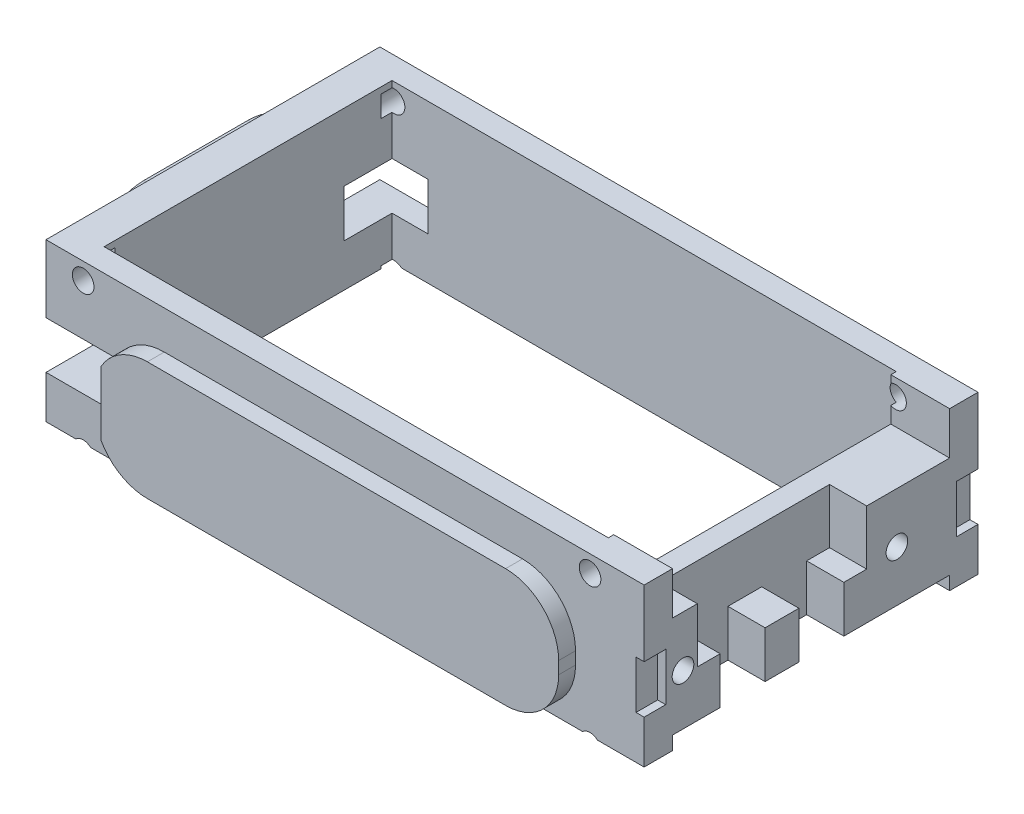
SolidWorks part; units mm, degrees
material "尼龙 101"
ref_plane "前视基准面" through (0, 0, 0) normal (0, 0, 1) x (1, 0, 0)
ref_plane "上视基准面" through (0, 0, 0) normal (0, 1, 0) x (1, 0, 0)
ref_plane "右视基准面" through (0, 0, 0) normal (1, 0, 0) x (0, 0, -1)
other "Configuration Table"
sketch "草图2" plane through (0, 0, 0) normal (0, 0, 1) x (1, 0, 0)
  line L1 (0, 0) -> (69, 0)
  line L2 (0, 0) -> (0, -17.83)
  line L3 (0, -17.83) -> (69, -17.83)
  line L4 (69, 0) -> (69, -17.83)
  dimension "D1" = 69
  dimension "D2" = 17.83
extrude "凸台-拉伸1" add sketch "草图2" along normal blind 2.5
fillet "圆角1" radius 8 4 edges at (69, 0, 1.25) (69, -17.83, 1.25) (0, -17.83, 1.25) (0, 0, 1.25)
sketch "草图3" plane through (0, 0, 0) normal (0, 0, -1) x (-1, 0, 0)
  line L0 (-61, 0) -> (-8, 0) construction
  line L1 (-79, 5.5) -> (9.5, 5.5)
  line L2 (-79, 5.5) -> (-79, -17.83)
  line L3 (-79, -17.83) -> (9.5, -17.83)
  line L4 (9.5, 5.5) -> (9.5, -17.83)
  line L5 (-8, -17.83) -> (-61, -17.83) construction
  line L6 (-69, -9.83) -> (-69, -8) construction
  line L7 (0, -8) -> (0, -9.83) construction
  dimension "D1" = 5.5
  dimension "D2" = 9.5
  dimension "D3" = 10
extrude "凸台-拉伸2" add sketch "草图3" along normal blind 4.2
sketch "草图4" plane through (-9.5, 0, 0) normal (-1, 0, 0) x (0, 0, 1)
  line L5 (-4.2, 5.5) -> (0, 5.5) construction
  line L6 (-4.2, -17.83) -> (-45.2, -17.83)
  line L7 (-4.2, -17.83) -> (-4.2, 5.5)
  line L8 (-4.2, 5.5) -> (-45.2, 5.5)
  line L9 (-45.2, -17.83) -> (-45.2, 5.5)
  dimension "D1" = 41
extrude "凸台-拉伸3" add sketch "草图4" against normal blind 6
sketch "草图5" plane through (0, 0, -45.2) normal (0, 0, -1) x (-1, 0, 0)
  line L1 (-79, 5.5) -> (9.5, 5.5)
  line L2 (-79, 5.5) -> (-79, -17.83)
  line L3 (-79, -17.83) -> (9.5, -17.83)
  line L4 (9.5, 5.5) -> (9.5, -17.83)
extrude "凸台-拉伸4" add sketch "草图5" along normal blind 4.2
sketch "草图6" plane through (0, 0, -49.4) normal (0, 0, -1) x (-1, 0, 0)
  line L4 (-69, -8) -> (-69, -9.83)
  line L5 (-8, 0) -> (-61, 0)
  line L6 (0, -9.83) -> (0, -8)
  line L7 (-61, -17.83) -> (-8, -17.83)
  line L8 (-69, -8) -> (-69, -9.83)
  line L9 (-8, 0) -> (-61, 0)
  line L10 (0, -9.83) -> (0, -8)
  line L11 (-61, -17.83) -> (-8, -17.83)
  arc A4 (-61, 0) -> (-69, -8) centre (-61, -8) ccw
  arc A5 (0, -8) -> (-8, 0) centre (-8, -8) ccw
  arc A6 (-8, -17.83) -> (0, -9.83) centre (-8, -9.83) ccw
  arc A7 (-69, -9.83) -> (-61, -17.83) centre (-61, -9.83) ccw
  arc A8 (-61, 0) -> (-69, -8) centre (-61, -8) ccw
  arc A9 (0, -8) -> (-8, 0) centre (-8, -8) ccw
  arc A10 (-8, -17.83) -> (0, -9.83) centre (-8, -9.83) ccw
  arc A11 (-69, -9.83) -> (-61, -17.83) centre (-61, -9.83) ccw
  dimension "D1" = 0
extrude "凸台-拉伸5" add sketch "草图6" along normal blind 2.5
sketch "草图7" plane through (-9.5, 0, 0) normal (-1, 0, 0) x (0, 0, 1)
  line L0 (-49.4, 0) -> (-49.4, -8) construction
  line L1 (-49.4, -4.5) -> (-38.9, -4.5)
  line L2 (-49.4, -4.5) -> (-49.4, -11.5)
  line L3 (-49.4, -11.5) -> (-38.9, -11.5)
  line L4 (-38.9, -4.5) -> (-38.9, -11.5)
  line L5 (-49.4, 5.5) -> (0, 5.5) construction
  line L6 (-24.7, 5.5) -> (-24.7, -17.83) construction
  line L7 (-49.4, -17.83) -> (0, -17.83) construction
  line L8 (0, -11.5) -> (-10.5, -11.5)
  line L9 (-10.5, -4.5) -> (-10.5, -11.5)
  line L10 (0, -4.5) -> (-10.5, -4.5)
  line L11 (0, -4.5) -> (0, -11.5)
  dimension "D1" = 10
  dimension "D2" = 10.5
  dimension "D3" = 7
extrude "切除-拉伸1" cut sketch "草图7" against normal blind 10.5
sketch "草图8" plane through (-3.5, 0, 0) normal (1, 0, 0) x (0, 0, -1)
  line L1 (4.2, 5.5) -> (45.2, 5.5)
  line L2 (4.2, 5.5) -> (4.2, -17.83)
  line L3 (4.2, -17.83) -> (45.2, -17.83)
  line L4 (45.2, 5.5) -> (45.2, -17.83)
sketch "草图9" plane through (-9.5, 0, 0) normal (-1, 0, 0) x (0, 0, 1)
  line L5 (-4.2, 5.5) -> (-45.2, 5.5) construction
  line L9 (-9, -19.5) -> (-40.4, -19.5)
  line L10 (-9, -19.5) -> (-9, 3.5)
  line L11 (-9, 3.5) -> (-40.4, 3.5)
  line L12 (-40.4, -19.5) -> (-40.4, 3.5)
  line L13 (-9, -19.5) -> (-40.4, 3.5) construction
  line L14 (-9, 3.5) -> (-40.4, -19.5) construction
  point P0 (-24.7, 5.5)
  point P1 (-24.7, -8)
  dimension "D1" = 2
  dimension "D2" = 31.4
  dimension "D3" = 23
extrude "凸台-拉伸6" add sketch "草图9" along normal blind 2.5 contours L10 L9 L12 L11
fillet "圆角3" radius 8 4 edges at (-10.75, -19.5, -9) (-10.75, 3.5, -9) (-10.75, 3.5, -40.4) (-10.75, -19.5, -40.4)
sketch "草图10" plane through (-9.5, 0, 0) normal (1, 0, 0) x (0, 0, -1)
  line L0 (40.4, -4.5) -> (38.9, -4.5) construction
  line L1 (38.9, -4.5) -> (38.9, -11.5) construction
  line L2 (37.2919, -17.83) -> (12.1081, -17.83)
  line L3 (17, -19.5) -> (32.4, -19.5)
  line L4 (37.2919, -17.83) -> (12.1081, -17.83)
  line L5 (17, -19.5) -> (32.4, -19.5)
  line L6 (38.9, -11.5) -> (40.4, -11.5) construction
  line L7 (40.4, -11.5) -> (40.4, -4.5) construction
  line L8 (9, -11.5) -> (10.5, -11.5) construction
  line L9 (10.5, -11.5) -> (10.5, -4.5) construction
  line L10 (10.5, -4.5) -> (9, -4.5) construction
  line L11 (9, -4.5) -> (9, -11.5) construction
  line L12 (40.4, -4.5) -> (38.9, -4.5)
  line L13 (38.9, -4.5) -> (38.9, -11.5)
  line L14 (38.9, -11.5) -> (40.4, -11.5)
  line L15 (40.4, -11.5) -> (40.4, -4.5)
  line L16 (9, -11.5) -> (10.5, -11.5)
  line L17 (10.5, -11.5) -> (10.5, -4.5)
  line L18 (10.5, -4.5) -> (9, -4.5)
  line L19 (9, -4.5) -> (9, -11.5)
  arc A2 (12.1081, -17.83) -> (17, -19.5) centre (17, -11.5) ccw
  arc A3 (32.4, -19.5) -> (37.2919, -17.83) centre (32.4, -11.5) ccw
  arc A4 (12.1081, -17.83) -> (17, -19.5) centre (17, -11.5) ccw
  arc A5 (32.4, -19.5) -> (37.2919, -17.83) centre (32.4, -11.5) ccw
  dimension "D1" = 0
sketch "草图11" plane through (79, 0, 0) normal (1, 0, 0) x (0, 0, -1)
  line L4 (49.3, -0.83) -> (33.05, -0.83)
  line L5 (33.05, -0.83) -> (33.05, -8.93)
  line L6 (33.05, -8.93) -> (29.55, -8.93)
  line L7 (29.55, -8.93) -> (29.55, -15.83)
  line L8 (29.55, -15.83) -> (49.3, -15.83)
  line L10 (0, -15.83) -> (11.25, -15.83)
  line L11 (11.25, -15.83) -> (11.25, -8.93)
  line L12 (11.25, -8.93) -> (7.75, -8.93)
  line L13 (7.75, -8.93) -> (7.75, -0.83)
  line L14 (7.75, -0.83) -> (0, -0.83)
  line L16 (0, -0.83) -> (0, -15.83)
  line L17 (49.3, -0.83) -> (49.3, -15.83)
  line L18 (4.2, -17.83) -> (0, -17.83) construction
  line L22 (0, 5.5) -> (0, -17.83) construction
  line L24 (17.9, -15.83) -> (22.9, -15.83)
  line L25 (17.9, -15.83) -> (17.9, -8.93)
  line L26 (17.9, -8.93) -> (22.9, -8.93)
  line L27 (22.9, -15.83) -> (22.9, -8.93)
  dimension "D1" = 7.75
  dimension "D2" = 8.1
  dimension "D3" = 3.5
  dimension "D4" = 6.9
  dimension "D5" = 18.3
  dimension "D6" = 15
  dimension "D7" = 3.5
  dimension "D8" = 16.25
  dimension "D9" = 15
  dimension "D10" = 5
  dimension "D12" = 0
  dimension "D13" = 6.65
  dimension "D14" = 2
  dimension "D15" = 6.9
  dimension "D16" = 0
extrude "凸台-拉伸7" add sketch "草图11" against normal blind 8.5
sketch "草图12" plane through (79, 0, 0) normal (1, 0, 0) x (0, 0, -1)
  line L9 (0, 5.5) -> (0, -17.83) construction
  line L10 (0, -11.43) -> (3.2, -11.43)
  line L11 (0, -11.43) -> (0, -4.33)
  line L12 (0, -4.33) -> (3.2, -4.33)
  line L13 (3.2, -11.43) -> (3.2, -4.33)
  line L17 (24.7, 5.5) -> (24.7, -17.83) construction
  line L18 (4.2, 5.5) -> (45.2, 5.5) construction
  line L19 (37.2919, -17.83) -> (12.1081, -17.83) construction
  line L20 (49.4, -4.33) -> (46.2, -4.33)
  line L21 (46.2, -11.43) -> (46.2, -4.33)
  line L22 (49.4, -11.43) -> (46.2, -11.43)
  line L23 (49.4, -11.43) -> (49.4, -4.33)
  line L24 (7.75, -0.83) -> (4.2, -0.83) construction
  dimension "D1" = 3.2
  dimension "D2" = 7.1
  dimension "D3" = 3.5
sketch "草图13" plane through (70.5, 0, 0) normal (-1, 0, 0) x (0, 0, 1)
  line L1 (-4.2, -15.83) -> (-45.2, -15.83)
  line L2 (-4.2, -15.83) -> (-4.2, -0.83)
  line L3 (-4.2, -0.83) -> (-45.2, -0.83)
  line L4 (-45.2, -15.83) -> (-45.2, -0.83)
  line L5 (-29.55, -15.83) -> (-45.2, -15.83) construction
  line L6 (-4.2, -0.83) -> (-4.2, -15.83) construction
  line L7 (-45.2, -0.83) -> (-45.2, -15.83) construction
  line L8 (-45.2, -0.83) -> (-33.05, -0.83) construction
extrude "凸台-拉伸8" add sketch "草图13" against normal blind 3
extrude "切除-拉伸3" cut sketch "草图12" against normal blind 1.2
extrude "切除-拉伸4" cut sketch "草图10" against normal blind 5
sketch "草图14" plane through (0, 0, -49.4) normal (0, 0, 1) x (1, 0, 0)
  line L3 (0.1762, -11.5) -> (1, -11.5)
  line L4 (1, -11.5) -> (1, -4.5)
  line L5 (0, -8) -> (0, -9.83)
  line L6 (0.1762, -11.5) -> (1, -11.5)
  line L7 (1, -11.5) -> (1, -4.5)
  line L8 (0, -8) -> (0, -9.83)
  line L10 (1, -4.5) -> (0.8063, -4.5)
  line L11 (1, -4.5) -> (0.8063, -4.5)
  arc A2 (0.8063, -4.5) -> (0, -8) centre (8, -8) ccw
  arc A3 (0, -9.83) -> (0.1762, -11.5) centre (8, -9.83) ccw
  arc A4 (0.8063, -4.5) -> (0, -8) centre (8, -8) ccw
  arc A5 (0, -9.83) -> (0.1762, -11.5) centre (8, -9.83) ccw
  dimension "D1" = 0
extrude "切除-拉伸5" cut sketch "草图14" against normal through all both and the other way through all
sketch "草图15" plane through (0, -11.5, 0) normal (0, 1, 0) x (1, 0, 0)
  line L0 (8, 49.4) -> (0.8063, 49.4) construction
  line L9 (1, 49.4) -> (0.1762, 49.4)
  line L10 (1, 49.4) -> (1, 51.9)
  line L11 (1, 51.9) -> (0.1762, 51.9)
  line L12 (0.1762, 49.4) -> (0.1762, 51.9)
  line L13 (1, 51.9) -> (1, 45.2) construction
  line L18 (1, -2.5) -> (0.1762, -2.5)
  line L19 (1, -2.5) -> (1, 0)
  line L20 (1, 0) -> (0.1762, 0)
  line L21 (0.1762, -2.5) -> (0.1762, 0)
extrude "切除-拉伸6" cut sketch "草图15" against normal through all both and the other way through all
sketch "草图18" plane through (70.5, 0, 0) normal (-1, 0, 0) x (0, 0, 1)
  line L4 (-45.2, -0.83) -> (-45.2, -15.83)
  line L5 (-45.2, -15.83) -> (-4.2, -15.83)
  line L6 (-4.2, -15.83) -> (-4.2, -0.83)
  line L7 (-4.2, -0.83) -> (-45.2, -0.83)
  line L8 (-45.2, -0.83) -> (-45.2, -15.83)
  line L9 (-45.2, -15.83) -> (-4.2, -15.83)
  line L10 (-4.2, -15.83) -> (-4.2, -0.83)
  line L11 (-4.2, -0.83) -> (-45.2, -0.83)
  dimension "D1" = 0
extrude "凸台-拉伸10" add sketch "草图18" along normal blind 1
sketch "草图16" plane through (79, 0, 0) normal (1, 0, 0) x (0, 0, -1)
  line L0 (45.2, -0.83) -> (45.2, -15.83) construction
  line L1 (45.2, -0.83) -> (33.05, -0.83) construction
  line L2 (29.55, -15.83) -> (45.2, -15.83) construction
  line L4 (45.2, 5.5) -> (45.2, -0.83) construction
  line L5 (45.2, -8.33) -> (5.1369, -8.33) construction
  line L7 (0, 5.5) -> (0, -4.33) construction
  line L8 (49.4, -8) -> (49.4, 0) construction
  circle A0 centre (37.4, -8.33) radius 1.6
  circle A1 centre (5.75, -8.33) radius 1.6
  point P6 (45.2, -8.33)
  dimension "D1" = 12
  dimension "D2" = 5.75
  dimension "D3" = 3.2
extrude "切除-拉伸7" cut sketch "草图16" against normal up to surface (9.5 mm away) and the other way through all up to face at (69.5, -8.33, -24.7)
sketch "草图19" plane through (69.5, 0, 0) normal (-1, 0, 0) x (0, 0, 1)
  line L1 (-37.4, -5.2123) -> (-40.1, -6.7712)
  line L2 (-40.1, -6.7712) -> (-40.1, -9.8888)
  line L3 (-40.1, -9.8888) -> (-37.4, -11.4477)
  line L4 (-37.4, -11.4477) -> (-34.7, -9.8888)
  line L5 (-34.7, -9.8888) -> (-34.7, -6.7712)
  line L6 (-34.7, -6.7712) -> (-37.4, -5.2123)
  line L7 (-5.75, -5.2123) -> (-8.45, -6.7712)
  line L8 (-8.45, -6.7712) -> (-8.45, -9.8888)
  line L9 (-8.45, -9.8888) -> (-5.75, -11.4477)
  line L10 (-5.75, -11.4477) -> (-3.05, -9.8888)
  line L11 (-3.05, -9.8888) -> (-3.05, -6.7712)
  line L12 (-3.05, -6.7712) -> (-5.75, -5.2123)
  circle A0 centre (-37.4, -8.33) radius 2.7 construction
  circle A1 centre (-5.75, -8.33) radius 2.7 construction
  dimension "D1" = 5.4
extrude "切除-拉伸8" cut sketch "草图19" against normal blind 3.6 and the other way blind 3
sketch "草图20" plane through (0, 0, 2.5) normal (0, 0, 1) x (1, 0, 0)
  line L5 (1.15, -4.1659) -> (1.15, -13.6641)
  line L6 (8, -17.68) -> (61, -17.68)
  line L7 (68.85, -9.83) -> (68.85, -8)
  line L12 (61, -0.15) -> (8, -0.15)
  line L13 (1, -4.127) -> (1, -13.703)
  line L14 (8, -17.83) -> (61, -17.83)
  line L15 (69, -9.83) -> (69, -8)
  line L16 (61, 0) -> (8, 0)
  line L17 (1, -4.127) -> (1, -13.703)
  line L18 (8, -17.83) -> (61, -17.83)
  line L19 (69, -9.83) -> (69, -8)
  line L20 (61, 0) -> (8, 0)
  arc A12 (1.15, -13.6641) -> (8, -17.68) centre (8, -9.83) ccw
  arc A13 (61, -17.68) -> (68.85, -9.83) centre (61, -9.83) ccw
  arc A14 (68.85, -8) -> (61, -0.15) centre (61, -8) ccw
  arc A15 (8, -0.15) -> (1.15, -4.1659) centre (8, -8) ccw
  arc A16 (1, -13.703) -> (8, -17.83) centre (8, -9.83) ccw
  arc A17 (61, -17.83) -> (69, -9.83) centre (61, -9.83) ccw
  arc A18 (69, -8) -> (61, 0) centre (61, -8) ccw
  arc A19 (8, 0) -> (1, -4.127) centre (8, -8) ccw
  arc A20 (1, -13.703) -> (8, -17.83) centre (8, -9.83) ccw
  arc A21 (61, -17.83) -> (69, -9.83) centre (61, -9.83) ccw
  arc A22 (69, -8) -> (61, 0) centre (61, -8) ccw
  arc A23 (8, 0) -> (1, -4.127) centre (8, -8) ccw
  dimension "D1" = 0
  dimension "D2" = 0.15
extrude "切除-拉伸9" cut sketch "草图20" against normal up to surface (2.5 mm away) up to face at (48.3567, -5.7455, 0)
sketch "草图21" plane through (0, 0, -51.9) normal (0, 0, -1) x (-1, 0, 0)
  line L0 (-1.15, -13.6641) -> (-1.15, -4.1659)
  line L1 (-8, -0.15) -> (-61, -0.15)
  line L2 (-68.85, -8) -> (-68.85, -9.83)
  line L3 (-61, -17.68) -> (-8, -17.68)
  line L4 (-1, -13.703) -> (-1, -4.127)
  line L5 (-8, 0) -> (-61, 0)
  line L6 (-69, -8) -> (-69, -9.83)
  line L7 (-61, -17.83) -> (-8, -17.83)
  line L8 (-1, -13.703) -> (-1, -4.127)
  line L9 (-8, 0) -> (-61, 0)
  line L10 (-69, -8) -> (-69, -9.83)
  line L11 (-61, -17.83) -> (-8, -17.83)
  arc A0 (-1.15, -4.1659) -> (-8, -0.15) centre (-8, -8) ccw
  arc A1 (-61, -0.15) -> (-68.85, -8) centre (-61, -8) ccw
  arc A2 (-68.85, -9.83) -> (-61, -17.68) centre (-61, -9.83) ccw
  arc A3 (-8, -17.68) -> (-1.15, -13.6641) centre (-8, -9.83) ccw
  arc A4 (-1, -4.127) -> (-8, 0) centre (-8, -8) ccw
  arc A5 (-61, 0) -> (-69, -8) centre (-61, -8) ccw
  arc A6 (-69, -9.83) -> (-61, -17.83) centre (-61, -9.83) ccw
  arc A7 (-8, -17.83) -> (-1, -13.703) centre (-8, -9.83) ccw
  arc A8 (-1, -4.127) -> (-8, 0) centre (-8, -8) ccw
  arc A9 (-61, 0) -> (-69, -8) centre (-61, -8) ccw
  arc A10 (-69, -9.83) -> (-61, -17.83) centre (-61, -9.83) ccw
  arc A11 (-8, -17.83) -> (-1, -13.703) centre (-8, -9.83) ccw
  dimension "D1" = 0
  dimension "D2" = 0.15
extrude "切除-拉伸10" cut sketch "草图21" against normal up to surface (2.5 mm away) up to face at (-1.9126, -14.6636, -49.4)
sketch "草图22" plane through (73.5, 0, 0) normal (1, 0, 0) x (0, 0, -1)
  line L0 (11.25, -8.93) -> (7.75, -8.93) construction
  line L1 (7.75, -0.83) -> (7.87, -0.83)
  line L2 (7.75, -0.83) -> (7.75, -8.93)
  line L3 (7.75, -8.93) -> (7.87, -8.93)
  line L4 (7.87, -0.83) -> (7.87, -8.93)
  line L5 (7.75, -0.83) -> (33.05, -0.83) construction
  line L6 (33.05, -8.93) -> (32.93, -8.93)
  line L7 (33.05, -8.93) -> (33.05, -0.83)
  line L8 (33.05, -0.83) -> (32.93, -0.83)
  line L9 (32.93, -8.93) -> (32.93, -0.83)
  dimension "D1" = 0.12
  dimension "D2" = 0.12
extrude "凸台-拉伸11" add sketch "草图22" along normal up to surface (5.5 mm away) up to face at (79, -8.33, -4.15)
sketch "草图23" plane through (-12, 0, 0) normal (-1, 0, 0) x (0, 0, 1)
  line L0 (-37.2405, -17.68) -> (-12.1595, -17.68)
  line L1 (-9.1514, -11.65) -> (-10.65, -11.65)
  line L2 (-10.65, -11.65) -> (-10.65, -4.35)
  line L3 (-10.65, -4.35) -> (-9.1514, -4.35)
  line L4 (-17, 3.35) -> (-32.4, 3.35)
  line L5 (-40.2486, -4.35) -> (-38.75, -4.35)
  line L6 (-38.75, -4.35) -> (-38.75, -11.65)
  line L7 (-38.75, -11.65) -> (-40.2486, -11.65)
  line L8 (-37.2919, -17.83) -> (-12.1081, -17.83)
  line L9 (-9, -11.5) -> (-10.5, -11.5)
  line L10 (-10.5, -11.5) -> (-10.5, -4.5)
  line L11 (-10.5, -4.5) -> (-9, -4.5)
  line L12 (-17, 3.5) -> (-32.4, 3.5)
  line L13 (-40.4, -4.5) -> (-38.9, -4.5)
  line L14 (-38.9, -4.5) -> (-38.9, -11.5)
  line L15 (-38.9, -11.5) -> (-40.4, -11.5)
  line L16 (-37.2919, -17.83) -> (-12.1081, -17.83)
  line L17 (-9, -11.5) -> (-10.5, -11.5)
  line L18 (-10.5, -11.5) -> (-10.5, -4.5)
  line L19 (-10.5, -4.5) -> (-9, -4.5)
  line L20 (-17, 3.5) -> (-32.4, 3.5)
  line L21 (-40.4, -4.5) -> (-38.9, -4.5)
  line L22 (-38.9, -4.5) -> (-38.9, -11.5)
  line L23 (-38.9, -11.5) -> (-40.4, -11.5)
  arc A0 (-40.2486, -11.65) -> (-37.2405, -17.68) centre (-32.4, -11.5) ccw
  arc A1 (-12.1595, -17.68) -> (-9.1514, -11.65) centre (-17, -11.5) ccw
  arc A2 (-9.1514, -4.35) -> (-17, 3.35) centre (-17, -4.5) ccw
  arc A3 (-32.4, 3.35) -> (-40.2486, -4.35) centre (-32.4, -4.5) ccw
  arc A4 (-40.4, -11.5) -> (-37.2919, -17.83) centre (-32.4, -11.5) ccw
  arc A5 (-12.1081, -17.83) -> (-9, -11.5) centre (-17, -11.5) ccw
  arc A6 (-9, -4.5) -> (-17, 3.5) centre (-17, -4.5) ccw
  arc A7 (-32.4, 3.5) -> (-40.4, -4.5) centre (-32.4, -4.5) ccw
  arc A8 (-40.4, -11.5) -> (-37.2919, -17.83) centre (-32.4, -11.5) ccw
  arc A9 (-12.1081, -17.83) -> (-9, -11.5) centre (-17, -11.5) ccw
  arc A10 (-9, -4.5) -> (-17, 3.5) centre (-17, -4.5) ccw
  arc A11 (-32.4, 3.5) -> (-40.4, -4.5) centre (-32.4, -4.5) ccw
  dimension "D1" = 0
  dimension "D2" = 0.15
extrude "切除-拉伸14" cut sketch "草图23" against normal up to surface (2.5 mm away) up to face at (-9.5, 0.4142, -24.7)
sketch "草图24" plane through (0, 5.5, 0) normal (0, 1, 0) x (1, 0, 0)
  line L0 (-4.3, 46) -> (-4.3, 3.4)
  line L1 (-3.5, 45.2) -> (69.5, 45.2)
  line L2 (-3.5, 45.2) -> (-3.5, 4.2)
  line L3 (-3.5, 4.2) -> (69.5, 4.2)
  line L4 (69.5, 45.2) -> (69.5, 4.2)
  line L5 (-4.3, 3.4) -> (70.3, 3.4)
  line L6 (70.3, 46) -> (70.3, 3.4)
  line L7 (-4.3, 46) -> (70.3, 46)
  dimension "D1" = 0.8
extrude "切除-拉伸15" cut sketch "草图24" against normal through all
sketch "草图25" plane through (0, 0, -49.4) normal (0, 0, -1) x (-1, 0, 0)
  line L0 (9.5, 5.5) -> (-79, 5.5) construction
  line L1 (9.5, -4.5) -> (9.5, 5.5) construction
  circle A0 centre (4, 3) radius 1.6
  circle A1 centre (4, -19) radius 1.6
  circle A2 centre (-71, 3) radius 1.6
  circle A3 centre (-71, -19) radius 1.6
  dimension "D1" = 3.2
  dimension "D4" = 2
  dimension "D6" = 75
  dimension "D7" = 22
  dimension "D2" = 2.5
  dimension "D3" = 5.5
  dimension "D5" = 2
extrude "切除-拉伸17" cut sketch "草图25" against normal blind 5
ref_plane "基准面1" through (0, 0, -24.7) normal (0, 0, 1) x (1, 0, 0)
mirror "镜向1" about plane through (0, 0, -24.7) normal (0, 0, 1) of "切除-拉伸17"
sketch "草图26" plane through (-9.5, 0, 0) normal (-1, 0, 0) x (0, 0, 1)
  line L0 (-49.4, -4.5) -> (-49.4, 5.5) construction
  line L1 (-49.4, 5.5) -> (0, 5.5) construction
  circle A0 centre (-47.2, -0.5) radius 1.6
  circle A1 centre (-2.2, -0.5) radius 1.6
  circle A2 centre (-2.2, -19) radius 1.6
  circle A3 centre (-47.2, -19) radius 1.6
  dimension "D1" = 3.2
  dimension "D2" = 2.2
  dimension "D3" = 6
  dimension "D4" = 2
  dimension "D5" = 2
extrude "切除-拉伸18" cut sketch "草图26" against normal blind 4
